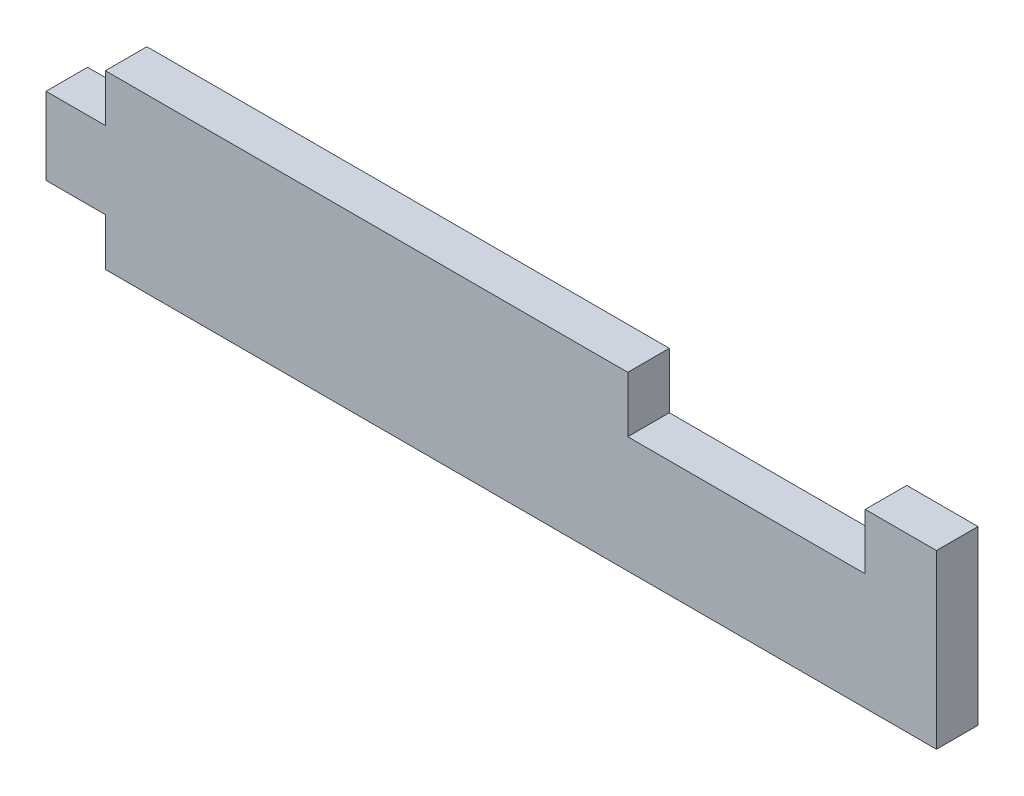
SolidWorks part; units mm, degrees
material "Pino"
ref_plane "Alzado" through (0, 0, 0) normal (0, 0, 1) x (1, 0, 0)
ref_plane "Planta" through (0, 0, 0) normal (0, 1, 0) x (1, 0, 0)
ref_plane "Vista lateral" through (0, 0, 0) normal (1, 0, 0) x (0, 0, -1)
sketch "Croquis1" plane through (0, 0, 0) normal (0, 0, 1) x (1, 0, 0)
  line L1 (-650, -72.5) -> (650, -72.5)
  line L2 (-650, -72.5) -> (-650, 72.5)
  line L3 (-650, 72.5) -> (650, 72.5)
  line L4 (650, -72.5) -> (650, 72.5)
  line L5 (-650, -72.5) -> (650, 72.5) construction
  line L6 (-650, 72.5) -> (650, -72.5) construction
  point P0 (0, 0)
  dimension "D1" = 1300
  dimension "D2" = 145
extrude "Saliente-Extruir1" add sketch "Croquis1" along normal blind 35
sketch "Croquis2" plane through (-650, 0, 0) normal (-1, 0, 0) x (0, 0, 1)
  line L0 (35, 72.5) -> (35, -72.5) construction
  line L1 (0, 72.5) -> (35, 72.5)
  line L2 (0, 72.5) -> (0, -72.5)
  line L3 (0, -72.5) -> (35, -72.5)
  line L4 (35, 72.5) -> (35, -72.5)
  dimension "D1" = 145
extrude "Cortar-Extruir1" cut sketch "Croquis2" against normal blind 600
sketch "Croquis3" plane through (-50, 0, 0) normal (-1, 0, 0) x (0, 0, 1)
  line L0 (0, 72.5) -> (0, -72.5) construction
  line L1 (0, 32.5) -> (35, 32.5)
  line L2 (0, 32.5) -> (0, -32.5)
  line L3 (0, -32.5) -> (35, -32.5)
  line L4 (35, 32.5) -> (35, -32.5)
  line L5 (0, 32.5) -> (35, 32.5) construction
  line L6 (35, -72.5) -> (35, 72.5) construction
  line L7 (35, -32.5) -> (0, -32.5) construction
extrude "Saliente-Extruir2" add sketch "Croquis3" along normal blind 50
sketch "Croquis4" plane through (0, 0, 35) normal (0, 0, 1) x (1, 0, 0)
  line L0 (650, -72.5) -> (650, 72.5) construction
  line L1 (390, 104.2424) -> (590, 104.2424)
  line L2 (390, 104.2424) -> (390, 25.5)
  line L3 (390, 25.5) -> (590, 25.5)
  line L4 (590, 104.2424) -> (590, 25.5)
  line L5 (-65.2, 25.5) -> (570, 25.5) construction
  point P6 (390, 64.8712)
  point P8 (398.9377, 47.4131)
  dimension "D1" = 60
  dimension "D2" = 260
  dimension "D3" = 0
extrude "Cortar-Extruir2" cut sketch "Croquis4" against normal up to surface (35 mm away) up to face at (112.5, 0, 0)
